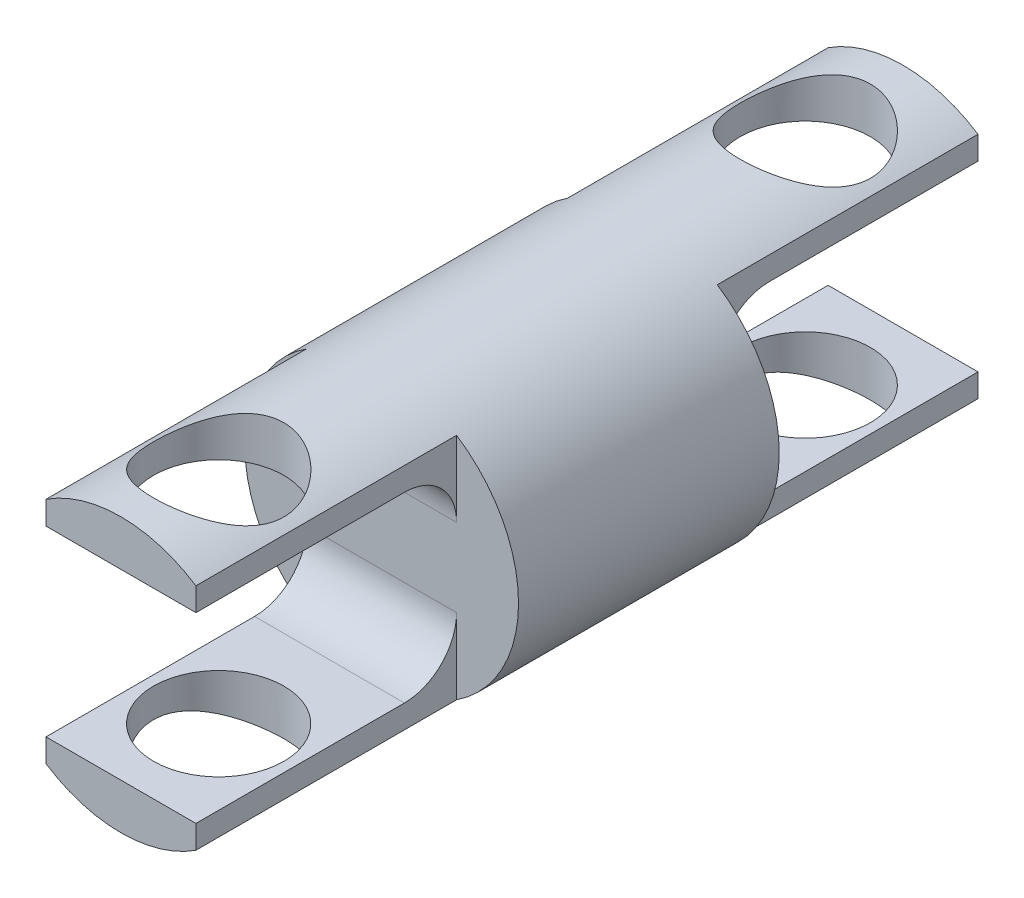
SolidWorks part; units mm, degrees
ref_plane "Płaszczyzna przednia" through (0, 0, 0) normal (0, 0, 1) x (1, 0, 0)
ref_plane "Płaszczyzna górna" through (0, 0, 0) normal (0, 1, 0) x (1, 0, 0)
ref_plane "Płaszczyzna prawa" through (0, 0, 0) normal (1, 0, 0) x (0, 0, -1)
sketch "Szkic1" plane through (0, 0, 0) normal (0, 0, 1) x (1, 0, 0)
  circle A0 centre (0, 0) radius 21
  dimension "D1" = 42
extrude "Dodanie-wyciągnięcie1" add sketch "Szkic1" along normal blind 20 contours A0
sketch "Szkic6" plane through (0, 0, 20) normal (0, 0, 1) x (1, 0, 0)
  line L0 (-11.5, 17.5713) -> (-11.5, 14)
  line L1 (-11.5, 14) -> (11.5, 14)
  line L2 (11.5, 14) -> (11.5, 17.5713)
  line L3 (0, 0) -> (13.4968, 0) construction
  line L4 (11.5, -14) -> (11.5, -17.5713)
  line L5 (-11.5, -14) -> (11.5, -14)
  line L6 (-11.5, -17.5713) -> (-11.5, -14)
  circle A0 centre (0, 0) radius 21 construction
  arc A1 (-11.5, -17.5713) -> (11.5, -17.5713) centre (0, 0) ccw
  arc A2 (11.5, 17.5713) -> (-11.5, 17.5713) centre (0, 0) ccw
  dimension "D1" = 14
  dimension "D2" = 11.5
  dimension "D3" = 11.5
extrude "Dodanie-wyciągnięcie4" add sketch "Szkic6" along normal blind 40
sketch "Szkic7" plane through (0, -14, 0) normal (0, 1, 0) x (1, 0, 0)
  line L0 (11.5, -60) -> (-11.5, -60) construction
  line L1 (11.5, -20) -> (-11.5, -20) construction
  circle A0 centre (0, -45) radius 10
  point P7 (0, -20)
  dimension "D1" = 20
  dimension "D2" = 15
extrude "Wytnij-wyciągnięcie1" cut sketch "Szkic7" along normal blind 40 and the other way up to next
fillet "Zaokrąglenie1" radius 8 2 edges at (0, -14, 20) (0, 14, 20)
mirror "Lustro2" about plane through (0, 0, 0) normal (0, 0, 1) of "Dodanie-wyciągnięcie1", "Zaokrąglenie1", "Wytnij-wyciągnięcie1", "Dodanie-wyciągnięcie4"
